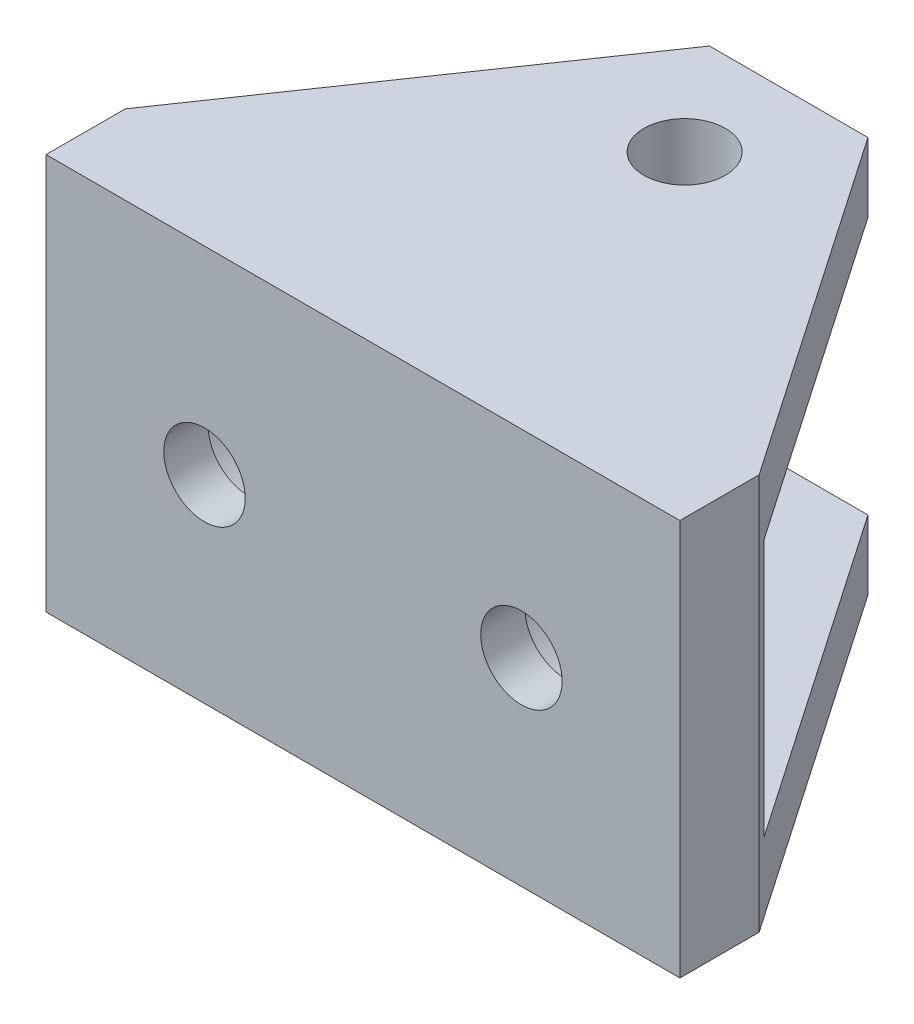
SolidWorks part; units mm, degrees
material "6061-T6 (SS)"
ref_plane "X-Y Datum" through (0, 0, 0) normal (0, 0, 1) x (1, 0, 0)
ref_plane "X-Z Datum" through (0, 0, 0) normal (0, 1, 0) x (1, 0, 0)
ref_plane "Y-Z Datum" through (0, 0, 0) normal (1, 0, 0) x (0, 0, -1)
sketch "Sketch1" plane through (0, 0, 0) normal (1, 0, 0) x (0, 0, -1)
  line L0 (0, 0) -> (0, 31.75)
  line L1 (0, 31.75) -> (38.4801, 31.75)
  line L2 (38.4801, 31.75) -> (38.4801, 26.2001)
  line L3 (38.4801, 26.2001) -> (7.62, 26.2001)
  line L4 (7.62, 26.2001) -> (7.62, 5.5499)
  line L5 (7.62, 5.5499) -> (38.4801, 5.5499)
  line L6 (38.4801, 5.5499) -> (38.4801, 0)
  line L7 (38.4801, 0) -> (0, 0)
  line L8 (25.7801, 31.75) -> (25.7801, 0) construction
  dimension "D1" = 20.6502
  dimension "D2" = 31.75
  dimension "D3" = 12.7
  dimension "D4" = 7.62
extrude "Boss-Extrude1" add sketch "Sketch1" along normal blind 50.8
sketch "Sketch2" plane through (0, 0, -7.62) normal (0, 0, -1) x (-1, 0, 0)
  line L0 (-50.8, 15.875) -> (0, 15.875) construction
  line L1 (-50.8, 5.5499) -> (-50.8, 26.2001) construction
  line L2 (0, 5.5499) -> (0, 26.2001) construction
  line L3 (-25.4, 5.5499) -> (-25.4, 26.2001) construction
  line L4 (-50.8, 5.5499) -> (0, 5.5499) construction
  line L5 (-50.8, 26.2001) -> (0, 26.2001) construction
  point P6 (-38.1, 15.875)
  point P7 (-12.7, 15.875)
  dimension "D1" = 25.4
  dimension "D2" = 12.7
hole_wizard "CBORE for 1/4 Binding Head Machine Screw1" positions "Sketch2" profile "Sketch3" counterbore size "1/4" standard "ANSI Inch" end condition through all
sketch "Sketch3" plane through (12.7, 15.875, -7.62) normal (1, 0, 0) x (0, 1, 0)
  line L0 (0, 0) -> (0, 7.62)
  line L1 (0, 7.62) -> (3.2639, 7.62)
  line L3 (3.2639, 7.62) -> (3.2639, 4.064)
  line L4 (3.2639, 4.064) -> (7.1437, 4.064)
  line L5 (7.1437, 4.064) -> (7.1437, 0)
  line L7 (7.1437, 0) -> (0, 0)
  line L11 (0, -6.35) -> (0, 107.95) construction
  dimension "Thru Hole Dia." = 6.5278
  dimension "Thru Hole Depth" = 7.62
  dimension "C'Bore Dia." = 14.2875
  dimension "C'Bore Depth" = 4.064
sketch "Sketch4" plane through (0, 0, 0) normal (0, -1, 0) x (1, 0, 0)
  line L0 (25.4, 0) -> (25.4, -38.4801) construction
  line L1 (50.8, 0) -> (0, 0) construction
  line L2 (50.8, -38.4801) -> (0, -38.4801) construction
  line L3 (19.05, -34.124) -> (0, -6.35)
  line L4 (31.75, -34.124) -> (50.8, -6.35)
  line L5 (0, -6.35) -> (0, -38.4801)
  line L6 (0, -38.4801) -> (50.8, -38.4801)
  line L7 (50.8, -38.4801) -> (50.8, -6.35)
  line L8 (0, 0) -> (0, -38.4801) construction
  line L9 (50.8, 0) -> (50.8, -38.4801) construction
  line L10 (19.05, -34.124) -> (31.75, -34.124)
  circle A0 centre (25.4, -25.7801) radius 3.2639
  point P10 (0, 0)
  point P21 (19.3912, -33.4001)
  point P22 (0, 0)
  dimension "D1" = 6.5278
  dimension "D2" = 6.35
  dimension "D3" = 5.08
  dimension "D4" = 12.7
extrude "Cut-Extrude1" cut sketch "Sketch4" against normal up to surface (31.75 mm away) up to face at (25.4, 31.75, -19.2401)
